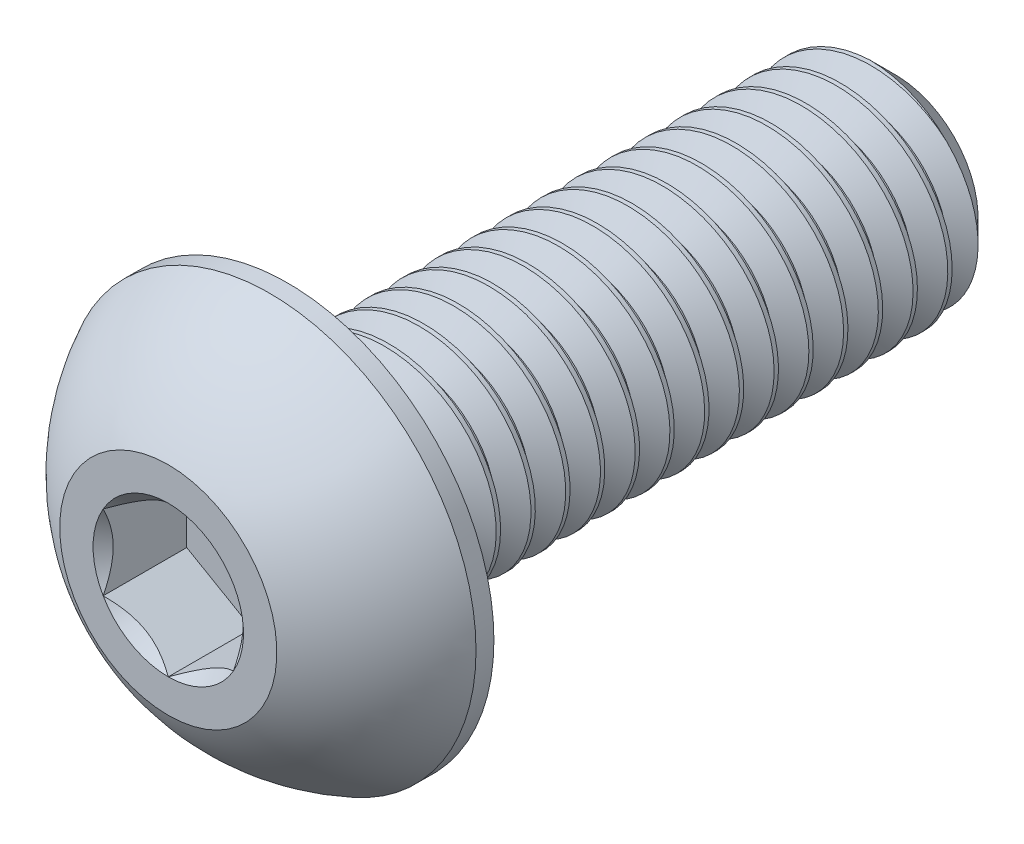
SolidWorks part; units mm, degrees
note: '?' marks a value the reader was unsure of.
ref_plane "Front" through (0, 0, 0) normal (0, 0, 1) x (1, 0, 0)
ref_plane "Top" through (0, 0, 0) normal (0, 1, 0) x (1, 0, 0)
ref_plane "Right" through (0, 0, 0) normal (1, 0, 0) x (0, 0, -1)
sketch "Sketch1" plane through (0, 0, 0) normal (1, 0, 0) x (0, 0, -1)
  line L2 (2.75, 2.5) -> (16.75, 2.5)
  line L3 (16.75, 2.5) -> (16.75, 0)
  line L4 (16.75, 0) -> (2.75, 0)
  line L6 (2.3375, 4.75) -> (2.75, 4.75) construction
  line L7 (16.75, 2.5) -> (16.75, -2.5) construction
  line L8 (0, 0) -> (2.75, 0) construction
  line L9 (2.75, 4.75) -> (2.75, -4.75) construction
  line L11 (2.75, 2.5) -> (2.75, 0)
  line L13 (0, 1.5) -> (0, -1.5) construction
  line L14 (0, 1.5) -> (0, 2.5) construction
  arc A3 (0, 2.5) -> (2.3375, 4.75) centre (4.6581, 0) cw construction
  dimension "D1" = 0.4125
revolve "Revolve1" add sketch "Sketch1" angle 360 mid plane about L4
sketch "Sketch3" plane through (0, 0, -16.75) normal (0, 0, -1) x (-1, 0, 0)
  circle A0 centre (0, 0) radius 2.5
curve "Helix/Spiral1" pitch 0.8 height 14.8 turns 18.5
chamfer "Chamfer1" distance 0.6 angle 45 1 edges at (-2.5, 0, -16.75)
sketch "Sketch7" plane through (0, 0, 0) normal (1, 0, 0) x (0, 0, -1)
  line L6 (2.3375, 4.75) -> (2.75, 4.75) construction
  line L8 (0, 0) -> (2.75, 0) construction
  line L11 (2.75, 4.75) -> (2.75, -4.75) construction
  line L12 (2.3375, 4.75) -> (2.75, 4.75)
  line L13 (0, 0) -> (2.75, 0)
  line L14 (0, 1.5) -> (0, -1.5) construction
  line L15 (2.75, 4.75) -> (2.75, 0)
  line L16 (0, 2.5) -> (0, 0)
  arc A2 (2.3375, 4.75) -> (0, 2.5) centre (4.6581, 0) ccw construction
  arc A3 (2.3375, 4.75) -> (0, 2.5) centre (4.6581, 0) ccw
revolve "Revolve2" add sketch "Sketch7" angle 360 mid plane about L13
sketch "Sketch5" plane through (0, 0, 0) normal (0, 0, 1) x (1, 0, 0)
  line L1 (1.5, -0.866) -> (1.5, 0.866)
  line L2 (1.5, 0.866) -> (0, 1.7321)
  line L3 (0, 1.7321) -> (-1.5, 0.866)
  line L4 (-1.5, 0.866) -> (-1.5, -0.866)
  line L5 (-1.5, -0.866) -> (0, -1.7321)
  line L6 (0, -1.7321) -> (1.5, -0.866)
  circle A0 centre (0, 0) radius 1.5 construction
extrude "Cut-Extrude2" cut sketch "Sketch5" against normal blind 1.925
sketch "Sketch6" plane through (0, 0, 0) normal (0, 0, 1) x (1, 0, 0)
  circle A0 centre (0, 0) radius 1.7321
extrude "Cut-Extrude3" cut sketch "Sketch6" against normal blind 1.925 draft 45
sketch "Sketch2" plane through (0, 0, 0) normal (1, 0, 0) x (0, 0, -1)
  line L0 (16.15, 2.5) -> (16.85, 2.5)
  line L1 (16.85, 2.5) -> (16.55, 1.9804)
  line L2 (16.55, 1.9804) -> (16.45, 1.9804)
  line L3 (16.45, 1.9804) -> (16.15, 2.5)
  line L4 (16.3, 2.2402) -> (16.7, 2.2402) construction
  dimension "D1" = 60
  dimension "D2" = 0.1
  dimension "D3" = 0.4
sweep "Cut-Sweep1" cut profiles "Sketch2" path "Helix/Spiral1"
sketch "Sketch10" plane through (0, 0, 0) normal (1, 0, 0) x (0, 0, -1)
  line L0 (16.75, 2.5) -> (16.75, -2.5) construction
  point P0 (15.55, -2.5)
  dimension "D1" = 1.2
ref_axis "Center Axis 1" through (0, 0, -8.1113) along (0, 0, 1)?
ref_plane "Contact Plane 1" through (0, 0, -2.75) normal (0, 0, -1) x (-1, 0, 0)
ref_plane "Contact Plane 2" through (0, 0, 0) normal (0, 0, 1) x (1, 0, 0)
equation "\"D3@Helix/Spiral1\" = \"Lg@Sketch1\" + \"D4@Helix/Spiral1\""
equation "\"D2@Sketch2\" = \"D4@Helix/Spiral1\" * .125"
equation "\"D3@Sketch2\" = \"D4@Helix/Spiral1\" * .5"
equation "\"D1@Chamfer1\" = \"D4@Helix/Spiral1\" * .75"
equation "\"D1@Cut-Extrude2\" = \"Head Ht@Sketch1\" * .7"
equation "\"D1@Sketch1\" = \"Head Ht@Sketch1\" * .15"
equation "\"D1@Sketch10\" = \"D4@Helix/Spiral1\" * 1.5"
equation "\"D1@Cut-Extrude3\" = \"D1@Cut-Extrude2\""
